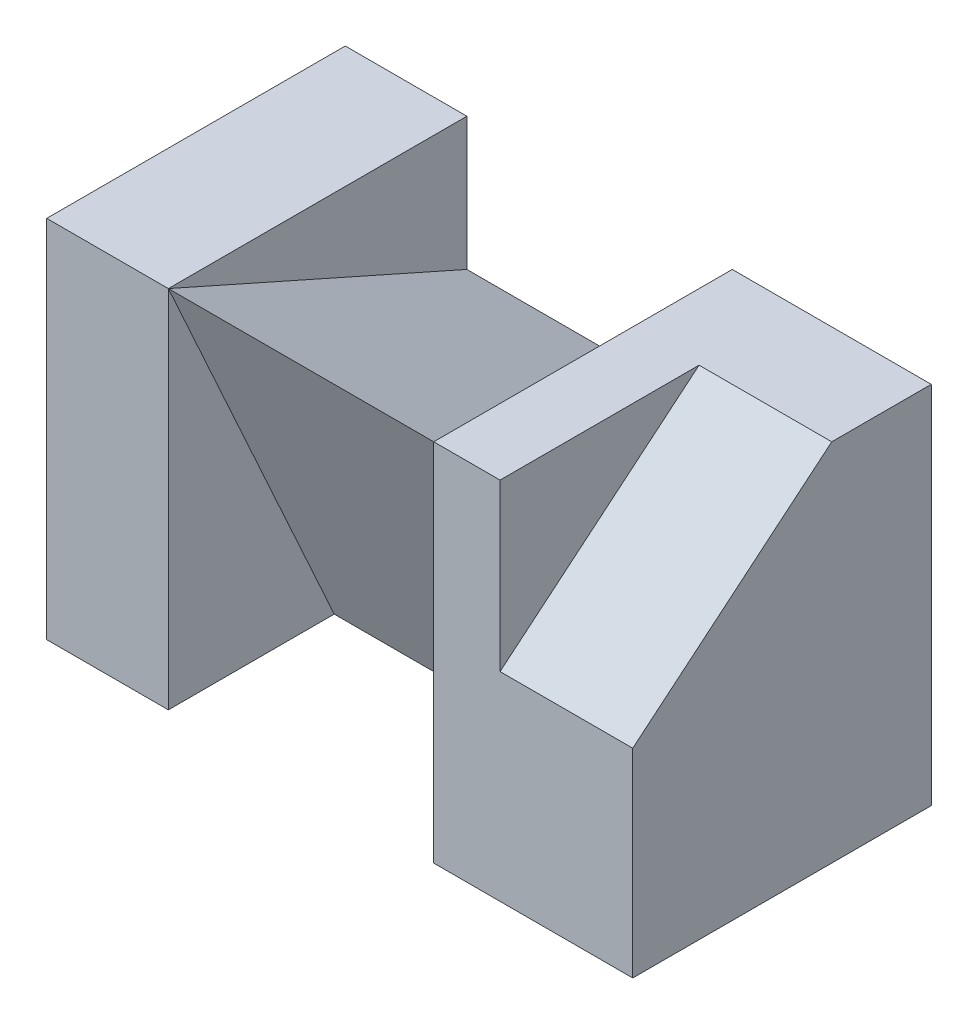
SolidWorks part; units mm, degrees
ref_plane "Front Plane" through (0, 0, 0) normal (0, 0, 1) x (1, 0, 0)
ref_plane "Top Plane" through (0, 0, 0) normal (0, 1, 0) x (1, 0, 0)
ref_plane "Right Plane" through (0, 0, 0) normal (1, 0, 0) x (0, 0, -1)
sketch "Sketch1" plane through (0, 0, 0) normal (0, 1, 0) x (1, 0, 0)
  line L0 (0, 0) -> (-8863.6337, 0) construction
  line L1 (0, 0) -> (0, -8863.6337) construction
  line L2 (-11, -13.5) -> (-24, 13.5)
  line L3 (-11, 13.5) -> (0, 13.5)
  line L4 (-11, 13.5) -> (-11, -13.5)
  line L5 (-11, -13.5) -> (0, -13.5)
  line L6 (0, 13.5) -> (0, -13.5)
  line L7 (-5.5, -13.5) -> (-5.5, 13.5) construction
  line L8 (-11, 0) -> (0, 0) construction
  line L9 (-24, 13.5) -> (-11, 13.5)
  line L11 (24, 13.5) -> (42, 13.5)
  line L12 (24, 13.5) -> (24, -13.5)
  line L13 (24, -13.5) -> (42, -13.5)
  line L14 (42, 13.5) -> (42, -13.5)
  line L15 (33, -13.5) -> (33, 13.5) construction
  line L16 (24, 0) -> (42, 0) construction
  line L17 (0, 13.5) -> (24, 13.5)
  line L18 (0, 13.5) -> (0, -13.5)
  line L19 (0, -13.5) -> (24, -13.5)
  line L20 (24, 13.5) -> (24, -13.5)
  point P5 (-5.5, 0)
  point P9 (33, 0)
  dimension "D1" = 11
  dimension "D2" = 27
  dimension "D3" = 18
  dimension "D4" = 27
  dimension "D5" = 24
  dimension "D6" = 13
extrude "Boss-Extrude1" add sketch "Sketch1" along normal blind 33 contours L6 L3 L4 L5 | L14 L11 L12 L13 region at (-5.5, 0, 0) region at (33, 0, 0)
extrude "Boss-Extrude2" add sketch "Sketch1<3>" along normal blind 13 contours L9 L2 L4 region at (-15.3333, 0, -4.5)
sketch "Sketch1<3>" plane through (0, 0, 0) normal (0, 1, 0) x (1, 0, 0) same geometry as "Sketch1"
sketch "Sketch3" plane through (24, 0, 0) normal (-1, 0, 0) x (0, 0, 1)
  line L0 (-13.5, 33) -> (-13.5, 21)
  line L1 (-13.5, 33) -> (-13.5, 13) construction
  line L2 (-13.5, 21) -> (13.5, 33)
  line L3 (13.5, 33) -> (-13.5, 33)
  line L4 (13.5, 0) -> (-1.5, 0)
  line L5 (13.5, 0) -> (-13.5, 0) construction
  line L6 (-1.5, 0) -> (13.5, 33)
  line L7 (13.5, 0) -> (13.5, 33)
  point P12 (0, 0)
  dimension "D1" = 12
  dimension "D2" = 15
extrude "Boss-Extrude4" add sketch "Sketch1<5>" along normal blind 33 contours L6 L19 L12 L17 region at (12, 0, 0)
sketch "Sketch1<5>" plane through (0, 0, 0) normal (0, 1, 0) x (1, 0, 0) same geometry as "Sketch1"
extrude "Cut-Extrude1" cut sketch "Sketch3" along normal blind 24 contours L3 L0 L2 | L6 L4 L7
sketch "Sketch4" plane through (42, 0, 0) normal (1, 0, 0) x (0, 0, -1)
  line L0 (4.5, 33) -> (-13.5, 18)
  line L1 (13.5, 33) -> (-13.5, 33) construction
  line L2 (-13.5, 18) -> (-13.5, 33)
  line L3 (-13.5, 33) -> (4.5, 33)
  line L4 (13.5, 33) -> (13.5, 0) construction
  line L5 (13.5, 0) -> (-13.5, 0) construction
  dimension "D1" = 9
  dimension "D2" = 18
extrude "Cut-Extrude2" cut sketch "Sketch4" against normal blind 12
